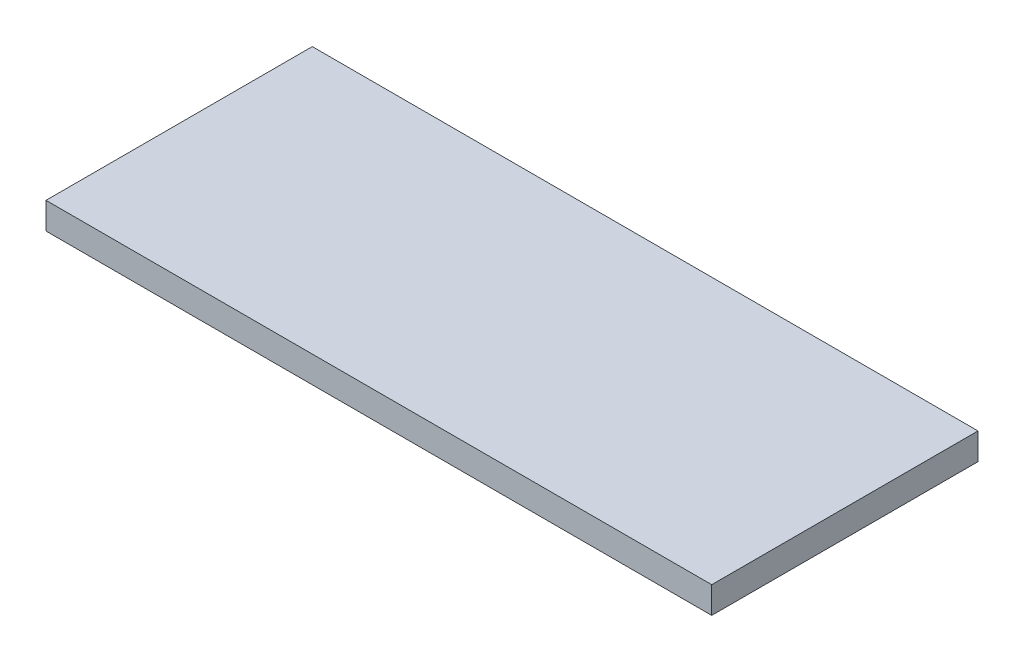
SolidWorks part; units mm, degrees
ref_plane "Front Plane" through (0, 0, 0) normal (0, 0, 1) x (1, 0, 0)
ref_plane "Top Plane" through (0, 0, 0) normal (0, 1, 0) x (1, 0, 0)
ref_plane "Right Plane" through (0, 0, 0) normal (1, 0, 0) x (0, 0, -1)
sketch "Sketch1" plane through (0, 0, 0) normal (0, 1, 0) x (1, 0, 0)
  line L1 (-25, 10) -> (25, 10)
  line L2 (-25, 10) -> (-25, -10)
  line L3 (-25, -10) -> (25, -10)
  line L4 (25, 10) -> (25, -10)
  line L5 (-25, 10) -> (25, -10) construction
  line L6 (-25, -10) -> (25, 10) construction
  point P0 (0, 0)
  dimension "D1" = 20
  dimension "D2" = 50
extrude "Boss-Extrude1" add sketch "Sketch1" along normal blind 2
